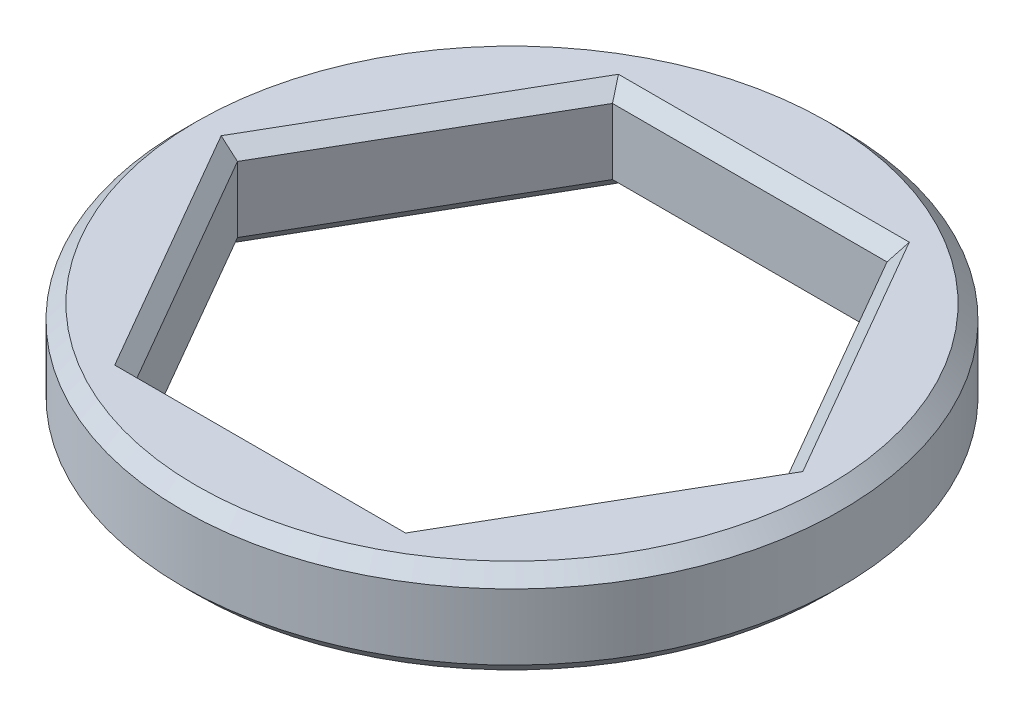
SolidWorks part; units mm, degrees
material "Markforged"
ref_plane "Front Plane" through (0, 0, 0) normal (0, 0, 1) x (1, 0, 0)
ref_plane "Top Plane" through (0, 0, 0) normal (0, 1, 0) x (1, 0, 0)
ref_plane "Right Plane" through (0, 0, 0) normal (1, 0, 0) x (0, 0, -1)
other "Bounding Box"
ref_plane "Default Plane" through (-8.9266, -12.7485, 0) normal (-0.1736, 0.9848, 0) x (0.9848, 0.1736, 0)
sketch "Sketch1" plane through (0, 0, 0) normal (0, 1, 0) x (1, 0, 0)
  line L1 (3.7028, -6.4135) -> (7.4057, 0)
  line L2 (7.4057, 0) -> (3.7028, 6.4135)
  line L3 (3.7028, 6.4135) -> (-3.7028, 6.4135)
  line L4 (-3.7028, 6.4135) -> (-7.4057, 0)
  line L5 (-7.4057, 0) -> (-3.7028, -6.4135)
  line L6 (-3.7028, -6.4135) -> (3.7028, -6.4135)
  circle A0 centre (0, 0) radius 6.4135 construction
  circle A1 centre (0, 0) radius 8.89
  dimension "D2" = 17.78
  dimension "D1" = 12.827
extrude "Boss-Extrude1" add sketch "Sketch1" along normal mid plane 2.54
chamfer "Chamfer1" distance 0.381 angle 45 14 edges at (0, -1.27, 8.89) (0, 1.27, 8.89) (-5.5543, -1.27, 3.2067) (-5.5543, -1.27, -3.2068) (0, -1.27, -6.4135) (5.5543, -1.27, -3.2068) (5.5543, -1.27, 3.2067) (0, -1.27, 6.4135) (5.5543, 1.27, -3.2068) (0, 1.27, -6.4135) (-5.5543, 1.27, -3.2068) (-5.5543, 1.27, 3.2067) (0, 1.27, 6.4135) (5.5543, 1.27, 3.2067)
